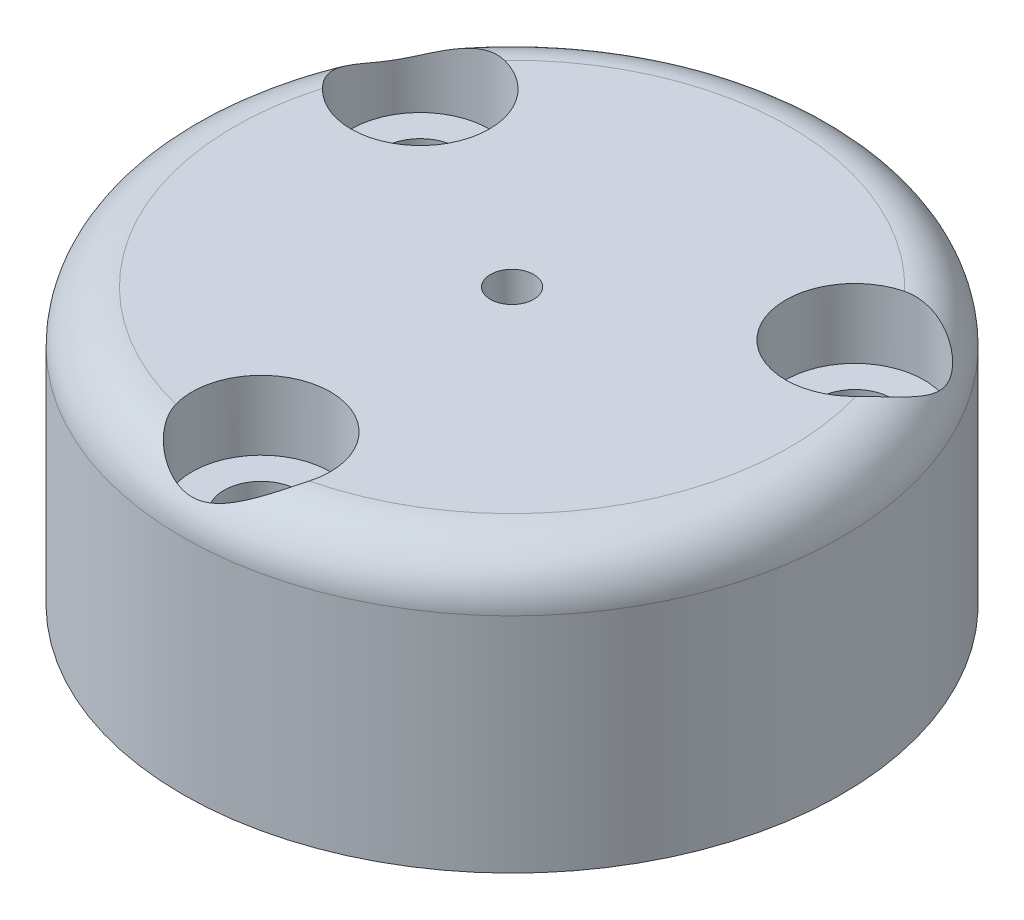
SolidWorks part; units mm, degrees
material "Stainless Steel (ferritic)"
ref_plane "Front Plane" through (0, 0, 0) normal (0, 0, 1) x (1, 0, 0)
ref_plane "Top Plane" through (0, 0, 0) normal (0, 1, 0) x (1, 0, 0)
ref_plane "Right Plane" through (0, 0, 0) normal (1, 0, 0) x (0, 0, -1)
sketch "Sketch1" plane through (0, 0, 0) normal (0, 1, 0) x (1, 0, 0)
  circle A0 centre (0, 0) radius 19.05
  dimension "D1" = 38.1
extrude "Boss-Extrude1" add sketch "Sketch1" along normal blind 15.875
sketch "Sketch2" plane through (0, 0, 0) normal (0, -1, 0) x (1, 0, 0)
  circle A0 centre (0, 0) radius 7
  dimension "D1" = 14
extrude "Cut-Extrude1" cut sketch "Sketch2" against normal blind 7
sketch "Sketch3" plane through (0, 7, 0) normal (0, -1, 0) x (1, 0, 0)
  circle A0 centre (0, 0) radius 6
  dimension "D1" = 12
extrude "Cut-Extrude2" cut sketch "Sketch3" against normal blind 7
hole_wizard "M3x0.5 Tapped Hole1" positions "Sketch5" profile "Sketch4" tap size "M3x0.5" standard "Ansi Metric" end condition through all
sketch "Sketch5" plane through (0, 14, 0) normal (0, -1, 0) x (1, 0, 0)
  point P0 (0, 0)
sketch "Sketch4" plane through (0, 14, 0) normal (1, 0, 0) x (0, 0, -1)
  line L0 (0, 0) -> (0, 1.875)
  line L1 (0, 1.875) -> (1.25, 1.875)
  line L2 (1.25, 1.875) -> (1.25, 0)
  line L5 (1.25, 0) -> (0, 0)
  line L11 (0, -6.35) -> (0, 107.95) construction
  dimension "Thru Tap Drill Dia." = 2.5
  dimension "Thru Tap Drill Depth" = 1.875
cosmetic thread "Hole Thread1" parameters "D2"=3
hole_wizard "CBORE for M4 SHCS1" positions "Sketch8" profile "Sketch7" counterbore size "M4" standard "Ansi Metric" end condition through all
sketch "Sketch8" plane through (0, 15.875, 0) normal (0, 1, 0) x (-1, 0, 0)
  line L0 (0, 0) -> (0, 15.1092) construction
  point P0 (0, 14.5)
  dimension "D1" = 14.5
sketch "Sketch7" plane through (0, 15.875, 14.5) normal (1, 0, 0) x (0, 0, 1)
  line L0 (0, 0) -> (0, 15.875)
  line L1 (0, 15.875) -> (2.15, 15.875)
  line L3 (2.15, 15.875) -> (2.15, 4)
  line L4 (2.15, 4) -> (4, 4)
  line L5 (4, 4) -> (4, 0)
  line L7 (4, 0) -> (0, 0)
  line L11 (0, -6.35) -> (0, 107.95) construction
  dimension "Thru Hole Dia." = 4.3
  dimension "Thru Hole Depth" = 15.875
  dimension "C'Bore Dia." = 8
  dimension "C'Bore Depth" = 4
pattern_circular "CirPattern1" count 3 over 360 about axis through (0, 15.875, 0) along (0, -1, 0) of "CBORE for M4 SHCS1"
fillet "Fillet1" radius 3 1 edges at (0, 15.875, 19.05)
sketch "Sketch9" plane through (0, 0, 0) normal (0, -1, 0) x (1, 0, 0)
  line L0 (0, 0) -> (-14.5, 0) construction
  line L1 (-14.5, 0) -> (-7.25, 12.5574) construction
  line L2 (-7.25, 12.5574) -> (0, 0) construction
  circle A0 centre (0, 0) radius 14.5 construction
  arc A1 (-6, 10.3923) -> (-8.5, 14.7224) centre (-7.25, 12.5574) ccw
  arc A2 (-17, 0) -> (-12, 0) centre (-14.5, 0) ccw
  arc A3 (-8.5, 14.7224) -> (-17, 0) centre (0, 0) ccw
  arc A4 (-6, 10.3923) -> (-12, 0) centre (0, 0) ccw
  dimension "D1" = 5
  dimension "D2" = 60
extrude "Cut-Extrude3" cut sketch "Sketch9" against normal blind 10
pattern_circular "CirPattern2" count 3 over 360 about axis through (0, 7, 0) along (0, -1, 0) of "Cut-Extrude3"
